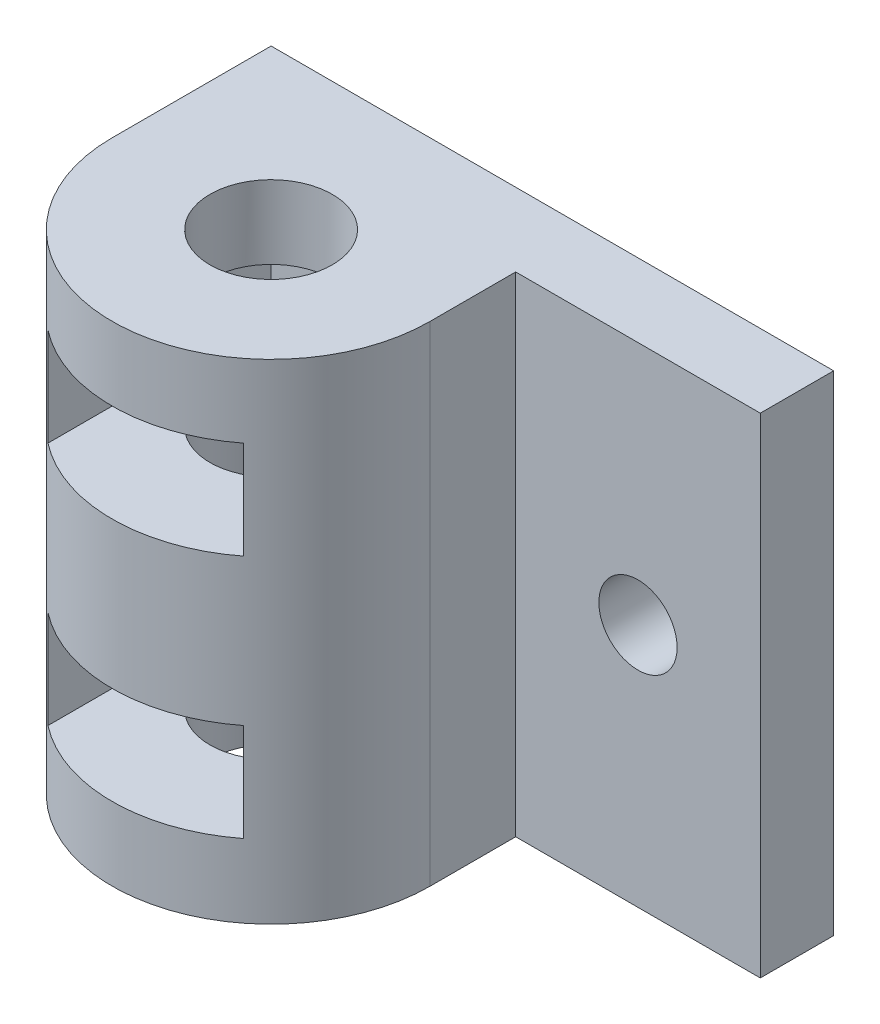
SolidWorks part; units mm, degrees
ref_plane "Front Plane" through (0, 0, 0) normal (0, 0, 1) x (1, 0, 0)
ref_plane "Top Plane" through (0, 0, 0) normal (0, 1, 0) x (1, 0, 0)
ref_plane "Right Plane" through (0, 0, 0) normal (1, 0, 0) x (0, 0, -1)
sketch "Sketch1" plane through (0, 0, 0) normal (0, 0, 1) x (1, 0, 0)
  line L1 (-10.5595, 5.237) -> (12.4405, 5.237)
  line L2 (-10.5595, 5.237) -> (-10.5595, -14.763)
  line L3 (-10.5595, -14.763) -> (12.4405, -14.763)
  line L4 (12.4405, 5.237) -> (12.4405, -14.763)
  dimension "D1" = 23
  dimension "D2" = 20
extrude "Boss-Extrude1" add sketch "Sketch1" along normal blind 3
sketch "Sketch2" plane through (0, 5.237, 0) normal (0, 1, 0) x (1, 0, 0)
  line L0 (12.4405, 0) -> (-10.5595, 0) construction
  line L1 (-10.5595, -3) -> (-10.5595, 0) construction
  line L2 (-4.0595, 0) -> (-4.0595, -13)
  line L3 (-10.5595, -3) -> (-10.5595, -6.5)
  line L4 (2.4405, -6.5) -> (2.4405, -3)
  line L5 (12.4405, -3) -> (-10.5595, -3) construction
  circle A0 centre (-4.0595, -6.5) radius 6.5
  circle A1 centre (-4.0595, -6.5) radius 2.5
  point P9 (-4.0595, -8.497)
  point P10 (-4.0595, -4.5)
  line M4 (-10.5595, -3) -> (12.4405, -3)
  dimension "D1" = 13
  dimension "D2" = 5
extrude "Boss-Extrude2" add sketch "Sketch2" against normal through all contours L2 A0 M4 | A1 L2 A0 M4 | A1 L2 A0 M4 | A0 L2 M4 | A0 L3 M4 | A0 L4 M4 region at (-1.9233, 5.237, 1.7726) region at (-6.1957, 5.237, 1.7726) region at (-0.7697, 5.237, 7.7182) region at (-7.3492, 5.237, 7.7182) region at (2.1383, 5.237, 3.8606) region at (-10.2573, 5.237, 3.8606)
ref_plane "Plane1" through (0, 0.237, 0) normal (0, -1, 0) x (-1, 0, 0)
sketch "Sketch4" plane through (0, 0.237, 0) normal (0, -1, 0) x (-1, 0, 0)
  line L0 (8.0595, -2.5) -> (0.0595, -10.5) construction
  line L1 (0.0595, -2.5) -> (8.0595, -2.5)
  line L2 (0.0595, -2.5) -> (0.0595, -10.5)
  line L4 (8.0595, -2.5) -> (8.0595, -10.5)
  line L5 (0.0595, -2.5) -> (8.0595, -10.5) construction
  line L8 (0.0595, -10.5) -> (0.0595, -14.5708)
  line L9 (0.0595, -14.5708) -> (8.0595, -14.5708)
  line L10 (8.0595, -10.5) -> (8.0595, -14.5708)
  circle A0 centre (4.0595, -6.5) radius 2.5 construction
  point P6 (4.0595, -6.5)
  dimension "D1" = 8
  dimension "D2" = 8
extrude "Cut-Extrude2" cut sketch "Sketch4" against normal mid plane 4 contours L9 L10 L4 L1 L2 L8
sketch "Sketch5" plane through (0, 0, 0) normal (0, 0, -1) x (-1, 0, 0)
  line L0 (-12.4405, -4.763) -> (10.5595, -4.763) construction
  line L1 (-12.4405, -14.763) -> (-12.4405, 5.237) construction
  line L2 (10.5595, 5.237) -> (10.5595, -14.763) construction
pattern_linear "LPattern2" count 2 spacing 10 along (0, -1, 0) of "Cut-Extrude2"
sketch "Sketch6" plane through (0, 0, 3) normal (0, 0, 1) x (1, 0, 0)
  line L0 (7.4405, 5.237) -> (7.4405, -14.763) construction
  line L1 (12.4405, 5.237) -> (2.4405, 5.237) construction
  line L2 (2.4405, -14.763) -> (12.4405, -14.763) construction
  circle A0 centre (7.4405, -4.763) radius 1.6
  dimension "D1" = 3.2
extrude "Cut-Extrude3" cut sketch "Sketch6" against normal blind 4
